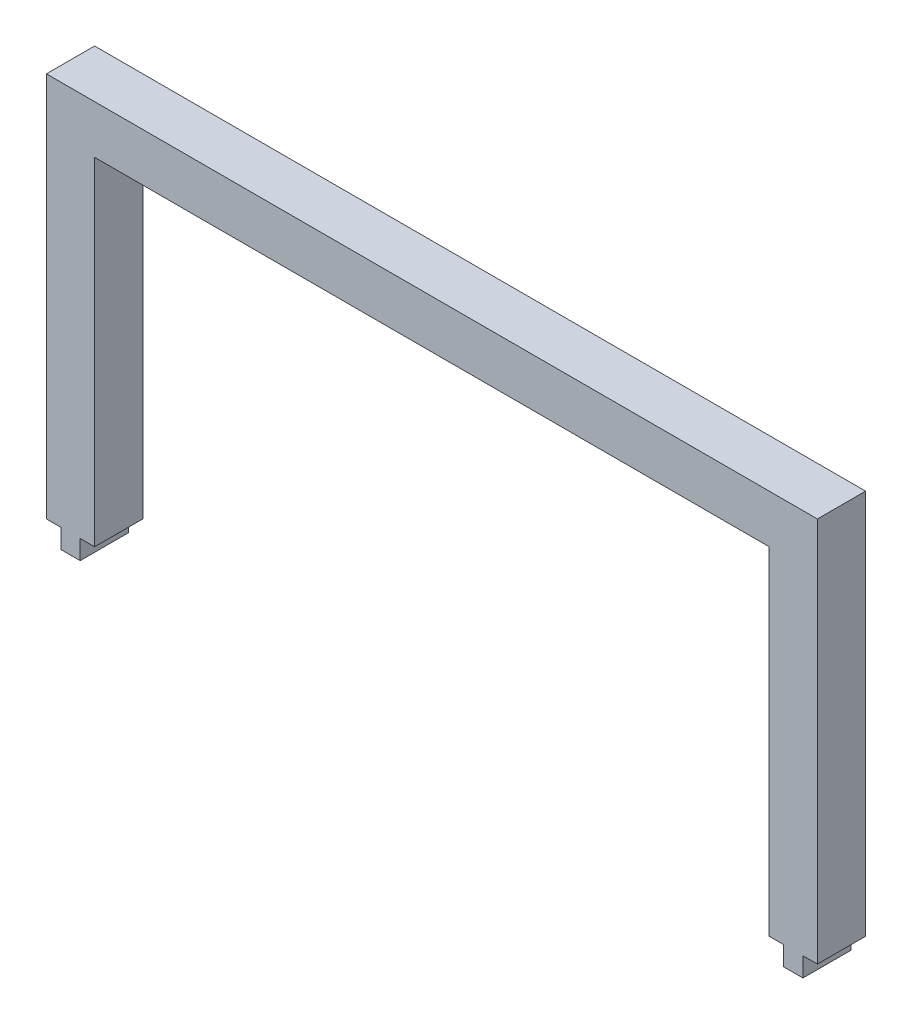
SolidWorks part; units mm, degrees
ref_plane "Front Plane" through (0, 0, 0) normal (0, 0, 1) x (1, 0, 0)
ref_plane "Top Plane" through (0, 0, 0) normal (0, 1, 0) x (1, 0, 0)
ref_plane "Right Plane" through (0, 0, 0) normal (1, 0, 0) x (0, 0, -1)
sketch "Sketch1" plane through (0, 0, 0) normal (0, 0, 1) x (1, 0, 0)
  line L1 (-502.8662, 247.1338) -> (297.1338, 247.1338)
  line L2 (-502.8662, 247.1338) -> (-502.8662, -152.8662)
  line L3 (-502.8662, -152.8662) -> (297.1338, -152.8662)
  line L4 (297.1338, 247.1338) -> (297.1338, -152.8662)
  line L5 (-487.8662, -152.8662) -> (-467.8662, -152.8662)
  line L6 (-487.8662, -152.8662) -> (-487.8662, -172.8662)
  line L7 (-487.8662, -172.8662) -> (-467.8662, -172.8662)
  line L8 (-467.8662, -152.8662) -> (-467.8662, -172.8662)
  line L9 (262.1338, -152.8662) -> (282.1338, -152.8662)
  line L10 (262.1338, -152.8662) -> (262.1338, -172.8662)
  line L11 (262.1338, -172.8662) -> (282.1338, -172.8662)
  line L12 (282.1338, -152.8662) -> (282.1338, -172.8662)
  line L13 (-452.8662, -152.8662) -> (247.1338, -152.8662)
  line L14 (-452.8662, -152.8662) -> (-452.8662, 197.1338)
  line L15 (-452.8662, 197.1338) -> (247.1338, 197.1338)
  line L16 (247.1338, -152.8662) -> (247.1338, 197.1338)
  dimension "D1" = 800
  dimension "D2" = 400
  dimension "D3" = 50
  dimension "D4" = 50
  dimension "D5" = 50
  dimension "D6" = 20
  dimension "D7" = 20
  dimension "D8" = 20
  dimension "D9" = 20
  dimension "D10" = 15
  dimension "D11" = 15
extrude "Boss-Extrude1" add sketch "Sketch1" along normal blind 50 contours L16 L3 L4 L1 L2 L14 L15 | L8 L3 L6 L7 | L12 L3 L10 L11 region at (-102.8662, 238.1895, 0) region at (-477.8662, -162.8662, 0) region at (272.1338, -162.8662, 0)
equation "\"ScannerWidth\"= 800"
equation "\"ScannerHeight\"= 400"
equation "\"ScannerThickness\"= 50"
equation "\"LegWidth\"= 20"
equation "\"LegDepth\"= 20"
equation "\"D1@Sketch1\"=\"ScannerWidth\""
equation "\"D2@Sketch1\"=\"ScannerHeight\""
equation "\"D3@Sketch1\"=\"ScannerThickness\""
equation "\"D4@Sketch1\"=\"ScannerThickness\""
equation "\"D5@Sketch1\"=\"ScannerThickness\""
equation "\"D6@Sketch1\"=\"LegWidth\""
equation "\"D7@Sketch1\"=\"LegDepth\""
equation "\"D8@Sketch1\"=\"LegDepth\""
equation "\"D9@Sketch1\"=\"LegDepth\""
equation "\"D10@Sketch1\"=(\"ScannerThickness\"-\"LegWidth\")/2"
equation "\"D11@Sketch1\"=(\"ScannerThickness\"-\"LegWidth\")/2"
equation "\"ScannerDepth\"= 50"
equation "\"D1@Boss-Extrude1\"=\"ScannerDepth\""
